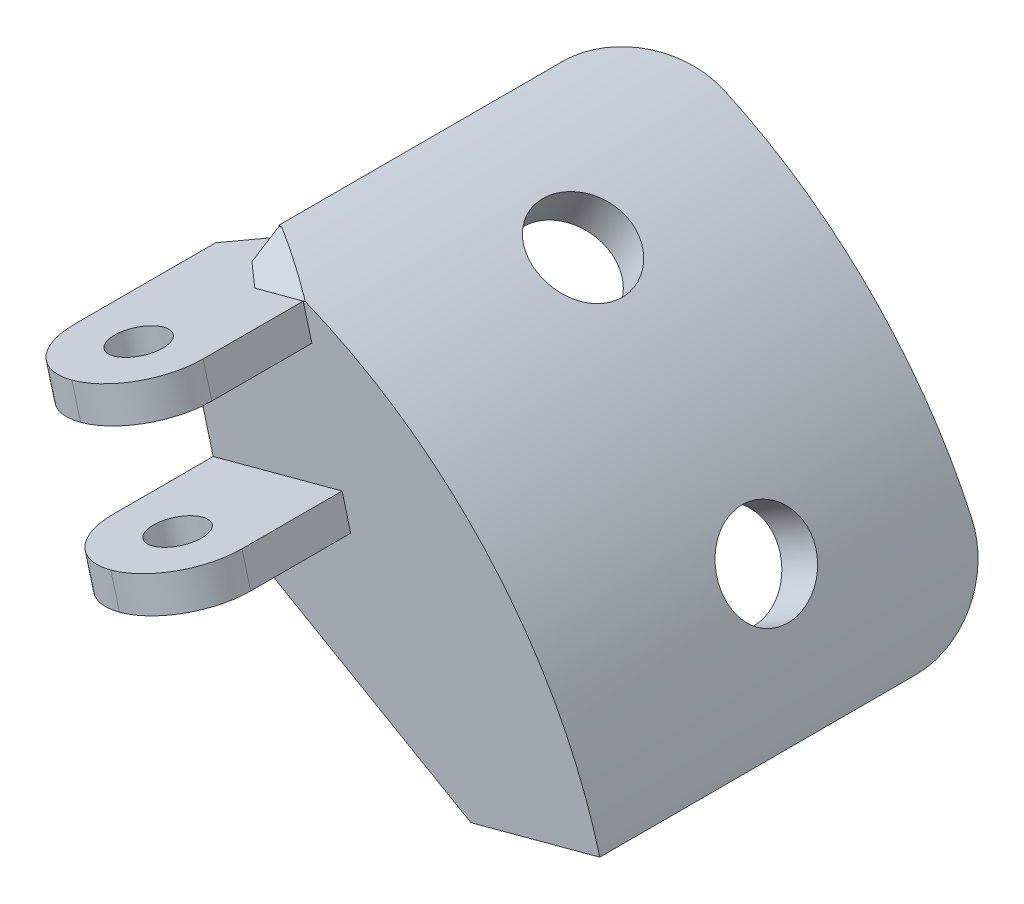
SolidWorks part; units mm, degrees
ref_plane "Front Plane" through (0, 0, 0) normal (0, 0, 1) x (1, 0, 0)
ref_plane "Top Plane" through (0, 0, 0) normal (0, 1, 0) x (1, 0, 0)
ref_plane "Right Plane" through (0, 0, 0) normal (1, 0, 0) x (0, 0, -1)
sketch "Sketch1" plane through (0, 0, 0) normal (0, 0, 1) x (1, 0, 0)
  line L0 (9.3581, 34.925) -> (9.861, 36.8018)
  line L11 (34.925, 9.3581) -> (25.5669, 25.5669)
  line L12 (25.5669, 25.5669) -> (9.3581, 34.925)
  line L13 (34.925, 9.3581) -> (36.8018, 9.861)
  line L15 (-17.4625, 30.2459) -> (-25.5669, 25.5669) [skipped]
  line L16 (-30.2459, 17.4625) -> (-34.925, 9.3581) [skipped]
  line L17 (-34.925, 0) -> (-34.925, -9.3581) [skipped]
  line L18 (-34.925, -9.3581) -> (-25.5669, -25.5669) [skipped]
  line L19 (-17.4625, -30.2459) -> (-9.3581, -34.925) [skipped]
  line L20 (0, -34.925) -> (9.3581, -34.925) [skipped]
  line L21 (9.3581, -34.925) -> (25.5669, -25.5669) [skipped]
  line L22 (30.2459, -17.4625) -> (34.925, -9.3581) [skipped]
  line L23 (34.925, -9.3581) -> (34.925, 9.3581) [skipped]
  line L24 (9.3581, 34.925) -> (0, 34.925) [skipped]
  arc A1 (36.8018, 9.861) -> (9.861, 36.8018) centre (0, 0) ccw
  arc A3 (33.735, 9.0393) -> (9.0393, 33.735) centre (0, 0) ccw construction
  dimension "D2" = 76.2
  dimension "D1" = 34.925
  dimension "D3" = 60
extrude "Boss-Extrude1" add sketch "Sketch1" along normal blind 27.94
sketch "Sketch3" plane through (17.4625, 30.2459, 0) normal (-0.5, -0.866, 0) x (-0.866, 0.5, 0)
  line L0 (9.3581, 0) -> (-9.3581, -27.94) construction
  line L1 (-9.3581, 0) -> (9.3581, -27.94) construction
  circle A0 centre (0, -13.97) radius 3.4925
  dimension "D1" = 6.985
extrude "Cut-Extrude1" cut sketch "Sketch3" against normal blind 5.08 contours A0
pattern_circular "CirPattern1" count 2 over 30 about axis through (0, 0, 27.94) along (0, 0, 1) of "Cut-Extrude1" reverse direction yes
fillet "Fillet2" radius 6.35 3 edges at (35.8634, 9.6096, 0) (9.6096, 35.8634, 0) (25.5669, 25.5669, 13.97)
sketch "Sketch7" plane through (0, 0, 27.94) normal (0, 0, 1) x (1, 0, 0)
  line L1 (12.2673, 3.287) -> (36.8018, 9.861)
  line L4 (4.4113, 32.6057) -> (14.3878, 35.2789)
  line L5 (4.4113, 32.6057) -> (12.2673, 3.287)
  line L7 (34.925, 9.3581) -> (36.8018, 9.861) construction
  arc A0 (14.3878, 35.2789) -> (36.8018, 9.861) centre (0, 0) cw
  arc A1 (36.8018, 9.861) -> (9.861, 36.8018) centre (0, 0) ccw construction
  dimension "D2" = 38.1
  dimension "D1" = 30.353
  dimension "D3" = 25.4
extrude "Boss-Extrude2" add sketch "Sketch7" along normal blind 2.54
sketch "Sketch8" plane through (0, 0, 30.48) normal (0, 0, 1) x (1, 0, 0)
  line L0 (4.4113, 32.6057) -> (14.2251, 35.2353)
  line L1 (14.2251, 35.2353) -> (14.8825, 32.7819)
  line L2 (14.8825, 32.7819) -> (5.0687, 30.1523)
  line L3 (4.4113, 32.6057) -> (12.2673, 3.287) construction
  line L4 (5.0687, 30.1523) -> (4.4113, 32.6057)
  line L5 (7.3696, 21.5652) -> (17.1834, 24.1948)
  line L6 (17.1834, 24.1948) -> (17.8408, 21.7414)
  line L7 (17.8408, 21.7414) -> (8.027, 19.1118)
  line L8 (8.027, 19.1118) -> (7.3696, 21.5652)
  dimension "D1" = 2.54
  dimension "D2" = 10.16
  dimension "D3" = 10.16
  dimension "D4" = 2.54
  dimension "D5" = 8.89
extrude "Boss-Extrude3" add sketch "Sketch8" along normal blind 12.7
fillet "Fillet3" radius 5.08 4 edges at (14.5538, 34.0086, 43.18) (17.5121, 22.9681, 43.18) (7.6983, 20.3385, 43.18) (4.74, 31.379, 43.18)
sketch "Sketch10" plane through (-4.2402, 15.8248, 0) normal (0.2588, -0.9659, 0) x (0.9659, 0.2588, 0)
  circle A0 centre (17.78, 38.1) radius 1.905
  arc A1 (22.86, 38.1) -> (17.78, 43.18) centre (17.78, 38.1) ccw construction
  dimension "D1" = 3.81
extrude "Cut-Extrude2" cut sketch "Sketch10" against normal blind 25.4
chamfer "Chamfer2" distance 2.54 angle 45 1 edges at (12.4608, 34.7626, 27.94)
chamfer "Chamfer3" distance 15.24 angle 45 1 edges at (12.2673, 3.287, 29.21)
sketch "Sketch11" plane through (0, 0, 27.94) normal (0, 0, -1) x (-1, 0, 0)
  line L0 (-26.4176, 24.0934) -> (-19.2588, 11.6939)
  line L1 (-26.988, 7.2314) -> (-8.3229, 18.0077) construction
  line L2 (-24.0934, 26.4176) -> (-16.5091, 13.2814)
  line L3 (-16.5091, 13.2814) -> (-19.2588, 11.6939)
  arc A0 (-26.4176, 24.0934) -> (-24.0934, 26.4176) centre (-20.9184, 20.9184) cw
  dimension "D2" = 6.35
  dimension "D1" = 3.175
extrude "Boss-Extrude4" add sketch "Sketch11" along normal blind 27.94
chamfer "Chamfer4" distance 12.7 angle 45 1 edges at (17.8839, 12.4876, 0)
chamfer "Chamfer5" distance 5.08 angle 45 2 edges at (17.3136, 30.3319, 27.94) (30.6713, 16.7257, 27.94)
